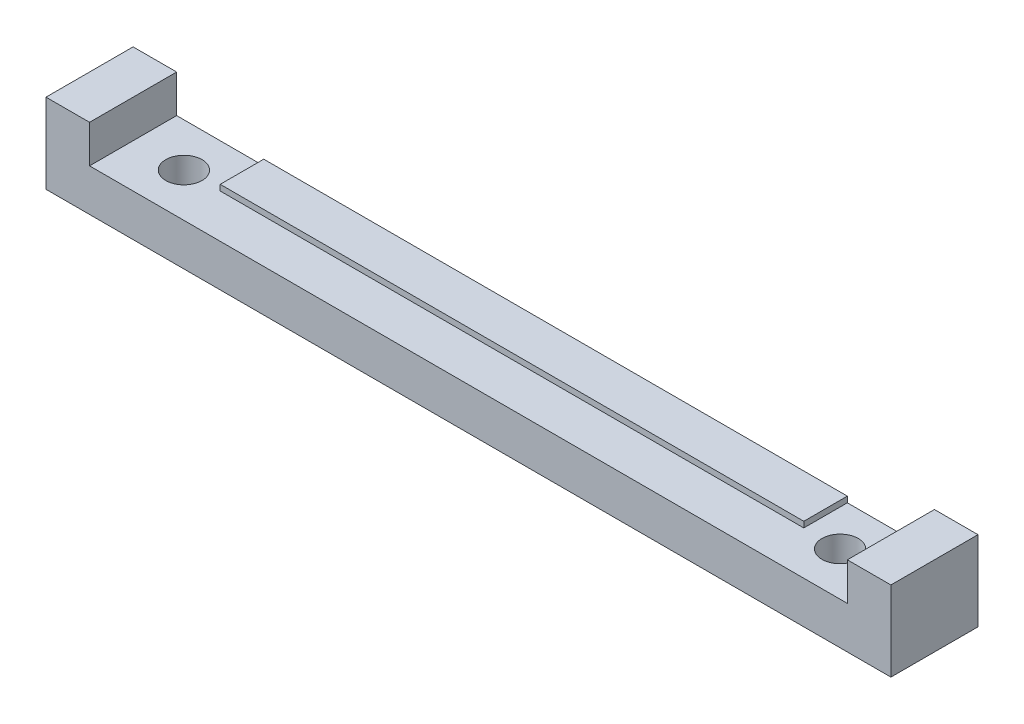
SolidWorks part; units mm, degrees
ref_plane "Front Plane" through (0, 0, 0) normal (0, 0, 1) x (1, 0, 0)
ref_plane "Top Plane" through (0, 0, 0) normal (0, 1, 0) x (1, 0, 0)
ref_plane "Right Plane" through (0, 0, 0) normal (1, 0, 0) x (0, 0, -1)
sketch "Sketch1" plane through (0, 0, 0) normal (0, 0, 1) x (1, 0, 0)
  line L0 (0, 5.5) -> (0, 0)
  line L1 (0, 0) -> (58.2, 0)
  line L2 (58.2, 0) -> (58.2, 5.5)
  line L3 (58.2, 5.5) -> (55.2, 5.5)
  line L4 (55.2, 5.5) -> (55.2, 2.9)
  line L5 (55.2, 2.9) -> (3, 2.9)
  line L6 (3, 2.9) -> (3, 5.5)
  line L7 (3, 5.5) -> (0, 5.5)
  dimension "D1" = 5.5
  dimension "D2" = 3
  dimension "D3" = 58.2
  dimension "D4" = 2.9
extrude "Boss-Extrude1" add sketch "Sketch1" along normal blind 6
sketch "Sketch4" plane through (0, 5.5, 0) normal (0, 1, 0) x (1, 0, 0)
  line L1 (3, -6) -> (0, -6) construction
  line L3 (0, -6) -> (0, 0) construction
  line L4 (58.2, -6) -> (58.2, 0) construction
  circle A0 centre (6.5, -3) radius 1.25
  circle A1 centre (51.7, -3) radius 1.25
  dimension "D1" = 2.5
  dimension "D2" = 6.5
  dimension "D3" = 3
  dimension "D4" = 6.5
extrude "Cut-Extrude3" cut sketch "Sketch4" against normal up to next
sketch "Sketch5" plane through (0, 2.9, 0) normal (0, 1, 0) x (1, 0, 0)
  line L0 (9, -3) -> (49.2, -3)
  line L2 (49.2, -3) -> (49.2, 0)
  line L3 (49.2, 0) -> (9, 0)
  line L4 (9, 0) -> (9, -3)
  line L5 (3, -6) -> (3, 0) construction
  line L6 (55.2, -6) -> (55.2, 0) construction
  line L8 (55.2, 0) -> (3, 0) construction
  dimension "D1" = 6
  dimension "D2" = 6
  dimension "D3" = 3
extrude "Boss-Extrude2" add sketch "Sketch5" along normal blind 0.4
